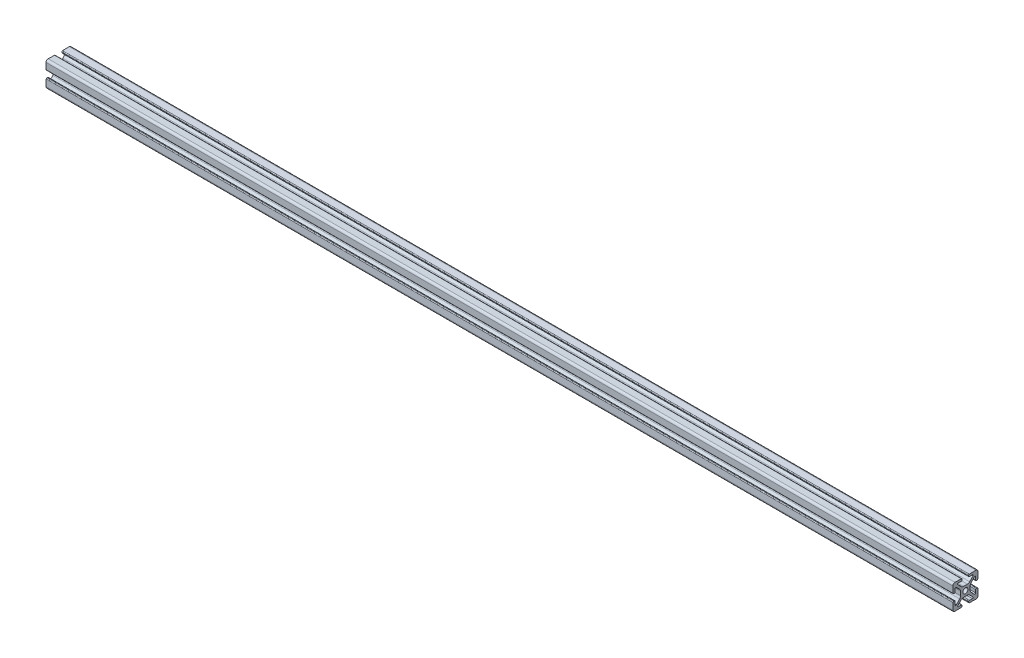
SolidWorks part; units mm, degrees
ref_plane "Front Plane" through (0, 0, 0) normal (0, 0, 1) x (1, 0, 0)
ref_plane "Top Plane" through (0, 0, 0) normal (0, 1, 0) x (1, 0, 0)
ref_plane "Right Plane" through (0, 0, 0) normal (1, 0, 0) x (0, 0, -1)
sketch "Sketch1" plane through (0, 0, 0) normal (1, 0, 0) x (0, 0, -1)
  line L0 (0, -12.7) -> (0, 12.7) construction
  line L1 (-7.874, 12.7) -> (7.874, 12.7) construction
  line L2 (-12.7, 0) -> (12.7, 0) construction
  line L3 (-7.874, 12.7) -> (-7.874, 4.826) construction
  line L4 (-3.302, 12.7) -> (3.302, 12.7) construction
  line L5 (-12.7, -12.7) -> (12.7, -12.7) construction
  line L6 (-12.7, 12.7) -> (12.7, 12.7) construction
  circle A0 centre (0, 0) radius 2.54 construction
  point P7 (0, 12.7)
  point P10 (0, 0)
  point P13 (0, 0)
  point P16 (0, 12.7)
  point P17 (-3.302, 12.7)
  point P18 (3.302, 12.7)
  point P21 (0, -12.7)
  point P24 (0, 12.7)
  dimension "Center Hole Diameter" = 5.08
  dimension "Rail Width" = 25.4
  dimension "Rail Height" = 25.4
  dimension "T-Slot Depth" = 7.874
  dimension "D1" = 15.748
  dimension "T-Slot Width" = 6.604
  dimension "D2" = 12.7
sketch "Sketch2" plane through (0, 0, 0) normal (0, 0, 1) x (1, 0, 0)
  line L0 (-457.2, 0) -> (457.2, 0) construction
  line L1 (0, 0) -> (0, 26.104) construction
  line L2 (457.2, -12.7) -> (457.2, 12.7) construction
  line L3 (-457.2, -12.7) -> (-457.2, 12.7) construction
  point P3 (-419.1, 0)
  point P8 (0, 0)
  point P9 (419.1, 0)
  point P12 (457.2, 0)
  point P15 (-457.2, 0)
  dimension "Length" = 914.4
  dimension "D1" = 38.1
  dimension "D2" = 25.4
sketch "Sketch3" plane through (0, 0, 0) normal (1, 0, 0) x (0, 0, -1)
  line L0 (0, 4.826) -> (1.9842, 4.826)
  line L1 (0, -12.7) -> (0, 12.7) construction
  line L2 (4.2293, 5.7559) -> (7.5866, 9.1132)
  line L6 (7.0212, 10.4136) -> (4.0906, 10.3112)
  line L7 (3.302, 11.0728) -> (3.302, 11.7082)
  line L8 (-7.874, 12.7) -> (7.874, 12.7) construction
  line L10 (0, 0) -> (12.7, 12.7) construction
  line L13 (0, 4.826) -> (0, 2.54)
  line L14 (4.826, 0) -> (2.54, 0)
  line L31 (4.826, 0) -> (4.826, 1.9842)
  line L32 (4.0374, 12.4697) -> (10.5971, 12.6988)
  line L33 (-12.7, 0) -> (12.7, 0) construction
  line L34 (-12.7, 12.7) -> (12.7, 12.7) construction
  line L35 (5.7559, 4.2293) -> (9.1132, 7.5866)
  line L36 (0, 12.7) -> (12.7, 12.7) construction
  line L37 (12.7, 12.7) -> (12.7, 8.0234) construction
  line L38 (11.0728, 3.302) -> (11.7082, 3.302)
  line L39 (10.4136, 7.0212) -> (10.3112, 4.0906)
  line L40 (12.6988, 10.5971) -> (12.4697, 4.0374)
  arc A0 (2.54, 0) -> (0, 2.54) centre (0, 0) ccw
  arc A1 (1.9842, 4.826) -> (4.2293, 5.7559) centre (1.9842, 8.001) ccw
  circle A2 centre (0, 0) radius 2.54 construction
  arc A7 (3.302, 11.7082) -> (4.0374, 12.4697) centre (4.064, 11.7082) cw
  arc A8 (4.0906, 10.3112) -> (3.302, 11.0728) centre (4.064, 11.0728) cw
  arc A14 (4.826, 1.9842) -> (5.7559, 4.2293) centre (8.001, 1.9842) cw
  arc A16 (10.5971, 12.6988) -> (12.6988, 10.5971) centre (10.668, 10.668) cw
  arc A17 (7.0212, 10.4136) -> (7.5866, 9.1132) centre (7.0478, 9.652) cw
  arc A18 (10.4136, 7.0212) -> (9.1132, 7.5866) centre (9.652, 7.0478) ccw
  arc A19 (10.3112, 4.0906) -> (11.0728, 3.302) centre (11.0728, 4.064) ccw
  arc A20 (11.7082, 3.302) -> (12.4697, 4.0374) centre (11.7082, 4.064) ccw
  point P37 (3.2994, 4.826)
  point P49 (12.7, 3.302)
  point P52 (3.302, 12.7)
  point P55 (3.302, 10.2837)
  dimension "D4" = 3.175
  dimension "D9" = 2.159
  dimension "D12" = 0.762
  dimension "D3" = 2.032
  dimension "D8" = 0.762
  dimension "D2" = 45
  dimension "D5" = 2
  dimension "D6" = 45
  dimension "D7" = 2.159
extrude "Boss-Extrude1" add sketch "Sketch3" against normal up to vertex (457.2 mm away) and the other way up to vertex (457.2 mm away) up to point (-457.2, 0, 0) other way up to point (457.2, 0, 0)
mirror "Mirror1" about plane through (0, 0, 0) normal (0, 1, 0) of bodies 104
mirror "Mirror2" about plane through (0, 0, 0) normal (0, 0, 1) of bodies 105
sketch "Sketch4" plane through (0, 0, 0) normal (0, 0, 1) x (1, 0, 0)
  line L1 (-459.74, -38.1) -> (459.74, -38.1)
  line L3 (457.2, 12.7) -> (457.2, -12.7)
  line L4 (457.2, -12.7) -> (-457.2, -12.7)
  line L5 (-457.2, -12.7) -> (-457.2, 12.7)
  line L6 (-457.2, 12.7) -> (-459.74, 12.7)
  line L7 (-459.74, 12.7) -> (-459.74, -38.1)
  line L8 (457.2, 12.7) -> (459.74, 12.7)
  line L9 (459.74, 12.7) -> (459.74, -38.1)
  dimension "D2" = 25.4
  dimension "D4" = 25.4
  dimension "D1" = 2.54
  dimension "D3" = 2.54
  dimension "D5" = 0
  dimension "D6" = 0
extrude "Cut-Extrude1" [suppressed] cut sketch "Sketch4" along normal blind 12.7 and the other way blind 12.7 contours L1 L9 L8 L3 L4 L5 L6 L7
ref_plane "Plane1" through (0, 0, 12.6988) normal (0, 0, 1) x (1, 0, 0)
ref_plane "Plane2" through (0, 12.6988, 0) normal (0, -1, 0) x (-1, 0, 0)
ref_plane "Plane3" through (0, 0, -12.6988) normal (0, 0, -1) x (-1, 0, 0)
ref_plane "Plane5" through (0, -12.6988, 0) normal (0, -1, 0) x (-1, 0, 0)
equation "\"D1@Sketch2\"=\"Rail Height@Sketch1\"*1.5"
equation "\"D2@Sketch2\"=\"Rail Height@Sketch1\""
equation "\"MaxLength\" = 36in"
equation "\"Length@Sketch2\"= \"MaxLength\""
equation "\"LeftCutAngle\"= 0deg"
equation "\"RightCutAngle\"= 0deg"
equation "\"BarThickness\"= 1in"
equation "\"InnerLength\"= \"MaxLength\" - TAN ( \"LeftCutAngle\" ) - TAN ( \"RightCutAngle\" )"
equation "\"RightBevelLength\"= tan ( \"RightCutAngle\" )"
equation "\"D2@Sketch4\"=\"BarThickness\""
equation "\"D4@Sketch4\"=\"BarThickness\""
equation "\"D1@Cut-Extrude1\"=\"BarThickness\"/2"
equation "\"D2@Cut-Extrude1\"=\"BarThickness\"/2"
equation "\"D5@Sketch4\"=\"LeftCutAngle\""
equation "\"D6@Sketch4\"=\"RightCutAngle\""
